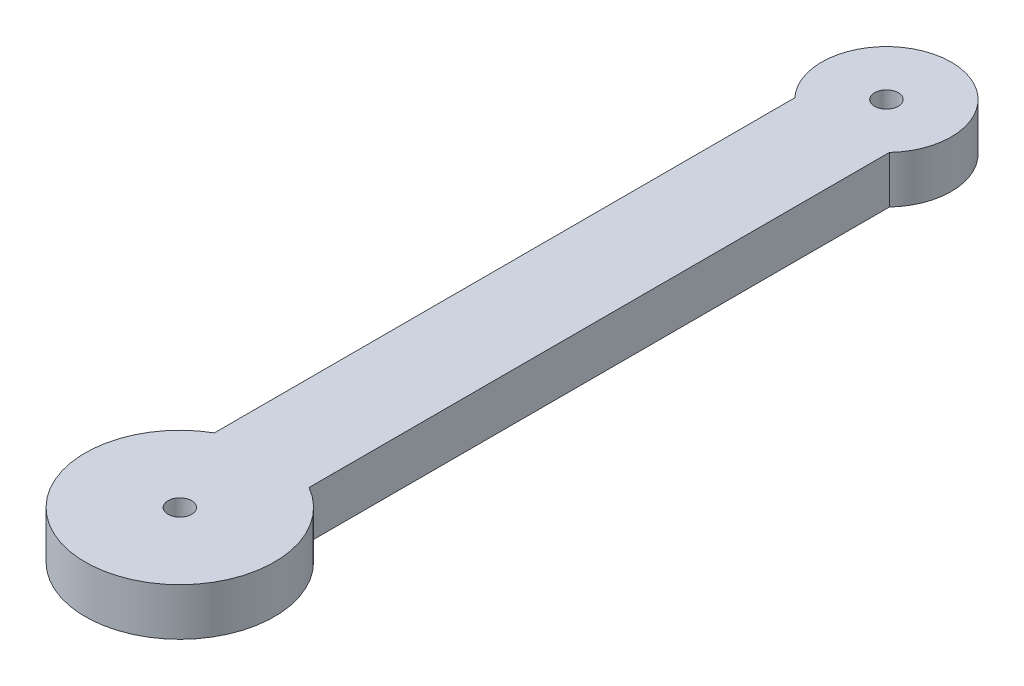
SolidWorks part; units mm, degrees
ref_plane "Front Plane" through (0, 0, 0) normal (0, 0, 1) x (1, 0, 0)
ref_plane "Top Plane" through (0, 0, 0) normal (0, 1, 0) x (1, 0, 0)
ref_plane "Right Plane" through (0, 0, 0) normal (1, 0, 0) x (0, 0, -1)
sketch "Sketch2" plane through (0, 0, 0) normal (0, 1, 0) x (1, 0, 0)
  line L0 (-2.5, 35) -> (-2.5, 4.3301)
  line L1 (2.5, 35) -> (2.5, 4.3301)
  circle A0 centre (0, 0) radius 0.625
  arc A1 (-2.5, 4.3301) -> (2.5, 4.3301) centre (0, 0) ccw
  circle A2 centre (0, 37.3428) radius 0.625
  arc A3 (2.5, 35) -> (-2.5, 35) centre (0, 37.3428) ccw
  dimension "D1" = 1.25
  dimension "D2" = 5
  dimension "D3" = 3.4261
  dimension "D4" = 2.5
  dimension "D5" = 35
extrude "Boss-Extrude1" add sketch "Sketch2" along normal blind 2.5
